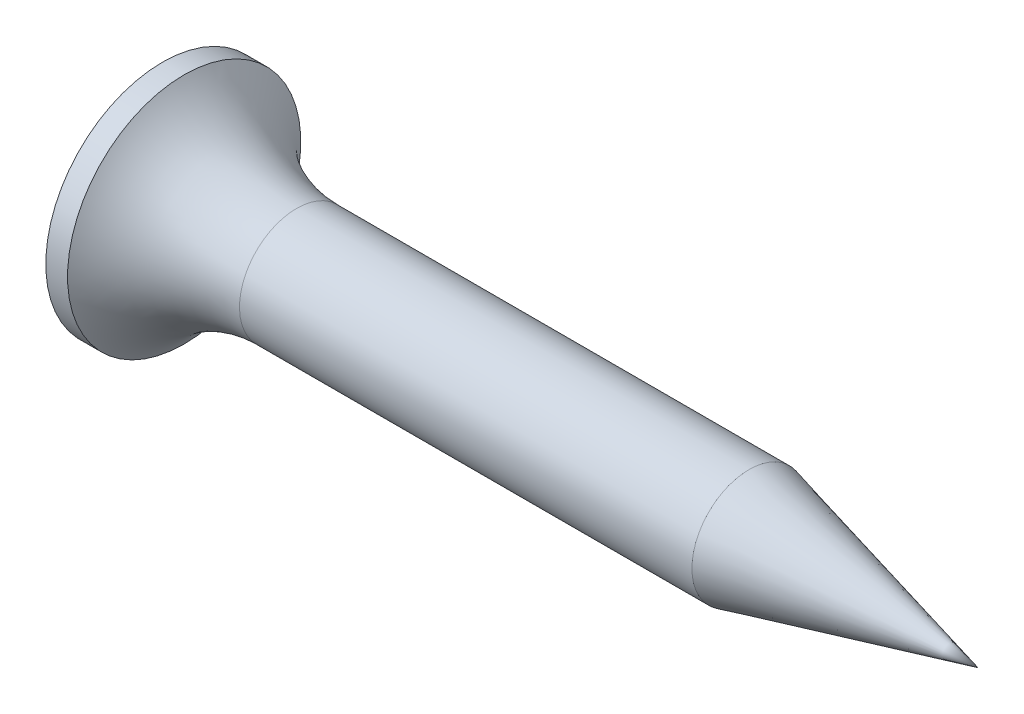
SolidWorks part; units mm, degrees
ref_plane "Front" through (0, 0, 0) normal (0, 0, 1) x (1, 0, 0)
ref_plane "Top" through (0, 0, 0) normal (0, 1, 0) x (1, 0, 0)
ref_plane "Right" through (0, 0, 0) normal (1, 0, 0) x (0, 0, -1)
sketch "Sketch1" plane through (0, 0, 0) normal (0, 0, 1) x (1, 0, 0)
  line L0 (30, 0) -> (21.5774, 2.1)
  line L1 (21.5774, 2.1) -> (4.9357, 2.1)
  line L2 (30, 0) -> (-110.3899, 0) construction
  line L3 (0.8, 4.29) -> (0, 4.29)
  line L4 (0, 4.29) -> (0, 0)
  line L5 (30, 0) -> (0, 0)
  arc A0 (4.9357, 2.1) -> (0.8, 4.29) centre (4.9357, 7.1) cw
  dimension "D1" = 14
revolve "Base" add sketch "Sketch1" angle 360 about L2
cosmetic thread "ThreadCosmetic1" [suppressed] parameters "D2"=3.7
sketch "Sketch3" plane through (0, 0, 0) normal (1, 0, 0) x (0, 0, -1)
  line L0 (0, 5.1262) -> (0, -0.6806) construction
  line L1 (-3.8942, 0) -> (0.672, 0) construction
  line L2 (0.5, 2.5) -> (-0.5, 2.5)
  line L3 (-0.5, 2.5) -> (-0.5, 0.5)
  line L4 (-0.5, 0.5) -> (-2.5, 0.5)
  line L5 (-2.5, 0.5) -> (-2.5, -0.5)
  line L6 (-0.5, -0.5) -> (-2.5, -0.5)
  line L7 (-0.5, -2.5) -> (-0.5, -0.5)
  line L8 (0.5, -2.5) -> (-0.5, -2.5)
  line L9 (0.5, -2.5) -> (0.5, -0.5)
  line L10 (0.5, -0.5) -> (2.5, -0.5)
  line L11 (2.5, 0.5) -> (2.5, -0.5)
  line L12 (0.5, 0.5) -> (2.5, 0.5)
  line L13 (0.5, 2.5) -> (0.5, 0.5)
  point P5 (2.5, 0)
  point P11 (-2.5, 0)
  point P15 (0, -2.5)
  point P20 (0, 2.5)
  dimension "D2" = 1
extrude "Cut-Extrude1" cut sketch "Sketch3" along normal blind 2.0314
draft "Draft1" type of draft neutral plane draft angle 30 faces to draft 4 face at (1.0157, 0, 2.5) face at (1.0157, 0, -2.5) face at (1.0157, -2.5, 0) face at (1.0157, 2.5, 0) neutral plane through (0, 4.29, 0) neutral plane normal (-1, 0, 0) parameters "D1"=30
sketch "Sketch4" plane through (0, 0, 0) normal (0, 0, 1) x (1, 0, 0)
  line L0 (4.9357, 2.35) -> (5.1857, 2.35)
  line L1 (5.1857, 2.35) -> (5.1857, 2.1)
  line L2 (5.1857, 2.1) -> (5.0607, 1.8835)
  line L3 (5.0607, 1.8835) -> (4.9357, 2.1)
  line L4 (4.9357, 2.1) -> (4.9357, 2.35)
  line L5 (0, 0) -> (4.4852, 0) construction
  line L6 (0, 4.29) -> (0, -4.29) construction
  line L7 (4.9357, 2.1) -> (4.9357, -2.1) construction
  dimension "D1" = 4.2
  dimension "D2" = 0.25
revolve "Cut-Revolve10" [suppressed] cut sketch "Sketch4" angle 360 about L5
pattern_linear "LPattern10" [suppressed] count 81 spacing 0.3 along (1, 0, 0) of bodies 103
equation "\"D2@Sketch3\" = \"m@Sketch3\" / 5"
equation "\"D2@ThreadCosmetic1\" = \"d@Sketch1\" - 0.5"
equation "\"D1@Sketch4\" = \"d@Sketch1\""
equation "\"D2@Sketch4\" = (  \"d@Sketch1\" - \"D2@ThreadCosmetic1\" )  / 2"
equation "\"D3@LPattern10\" = \"D2@Sketch4\" * 1.2"
equation "\"D1@LPattern10\" = (  \"l@Sketch1\" - \"c@Sketch1\" - \"r@Sketch1\" )  / \"D3@LPattern10\""
